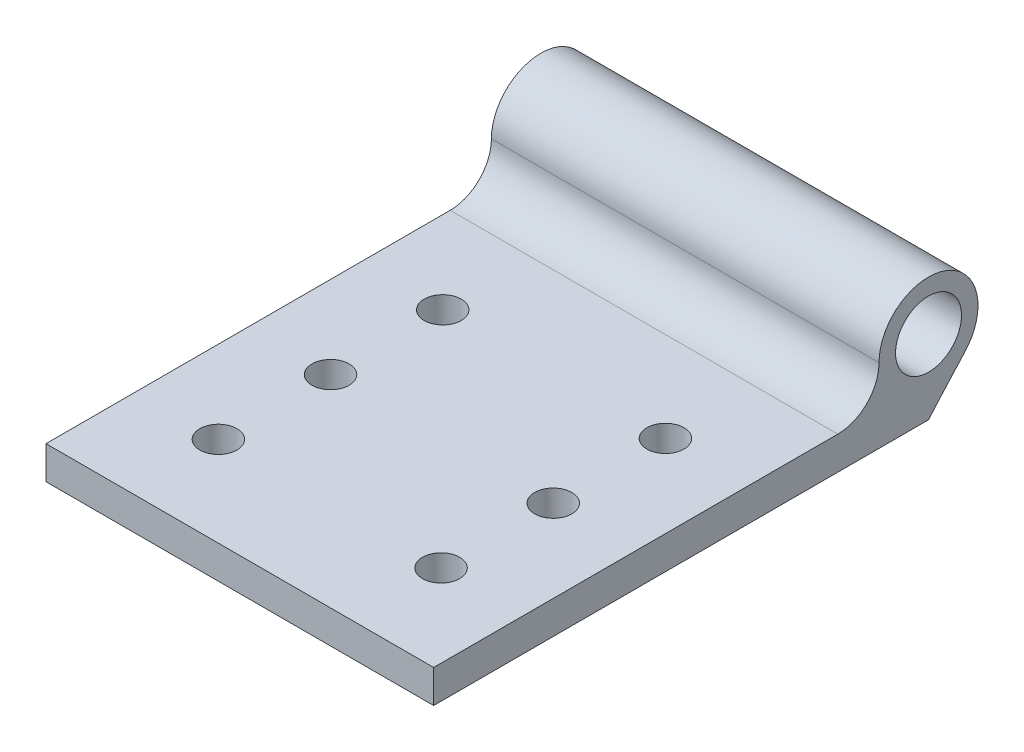
SolidWorks part; units mm, degrees
ref_plane "Front Plane" through (0, 0, 0) normal (0, 0, 1) x (1, 0, 0)
ref_plane "Top Plane" through (0, 0, 0) normal (0, 1, 0) x (1, 0, 0)
ref_plane "Right Plane" through (0, 0, 0) normal (1, 0, 0) x (0, 0, -1)
sketch "Sketch1" plane through (0, 0, 0) normal (0, 0, 1) x (1, 0, 0)
  line L1 (-11.75, 2) -> (11.75, 2)
  line L2 (-11.75, 2) -> (-11.75, 0)
  line L3 (-11.75, 0) -> (11.75, 0)
  line L4 (11.75, 2) -> (11.75, 0)
  point P4 (0, 0)
  dimension "D1" = 23.5
  dimension "D2" = 2
extrude "Boss-Extrude1" add sketch "Sketch1" along normal blind 30
sketch "Sketch2" plane through (11.75, 0, 0) normal (1, 0, 0) x (0, 0, -1)
  line L0 (0, 0) -> (0, 2) construction
  line L1 (-30, 2) -> (0, 2) construction
  circle A0 centre (0, 4.5) radius 2
  circle A1 centre (0, 4.5) radius 3
  dimension "D1" = 4
  dimension "D3" = 2.5
  dimension "D2" = 1
extrude "Boss-Extrude2" add sketch "Sketch2" against normal blind 23.5
fillet "Fillet1" radius 110 1 edges at (0, 1.5, 0)
fillet "Fillet2" radius 2.5 1 edges at (0, 2, 1.6583)
sketch "Sketch3" plane through (0, 2, 0) normal (0, 1, 0) x (1, 0, 0)
  line L0 (-6.75, -5.5) -> (-6.75, -30) construction
  line L1 (11.75, -5.5) -> (-11.75, -5.5) construction
  line L2 (6.75, -5.5) -> (6.75, -30) construction
  line L3 (-11.75, -10.95) -> (11.75, -10.95) construction
  line L4 (-11.75, -17.75) -> (11.75, -17.75) construction
  line L5 (-11.75, -30) -> (-11.75, -5.5) construction
  line L6 (11.75, -30) -> (11.75, -5.5) construction
  line L7 (-11.75, -24.55) -> (11.75, -24.55) construction
  line L8 (0, 0) -> (0, -29.0613) construction
  line L9 (-6.75, -5.5) -> (0, -5.5) construction
  line L10 (6.75, -5.5) -> (0, -5.5) construction
  line L11 (11.75, -10.95) -> (11.75, -17.75) construction
  line L12 (11.75, -24.55) -> (11.75, -17.75) construction
  circle A0 centre (-6.75, -10.95) radius 1.125
  circle A1 centre (-6.75, -17.75) radius 1.125
  circle A2 centre (-6.75, -24.55) radius 1.125
  circle A3 centre (6.75, -24.55) radius 1.125
  circle A4 centre (6.75, -17.75) radius 1.125
  circle A5 centre (6.75, -10.95) radius 1.125
  dimension "D1" = 2.25
  dimension "D2" = 6.75
  dimension "D3" = 6.8
extrude "Cut-Extrude1" cut sketch "Sketch3" against normal blind 24
